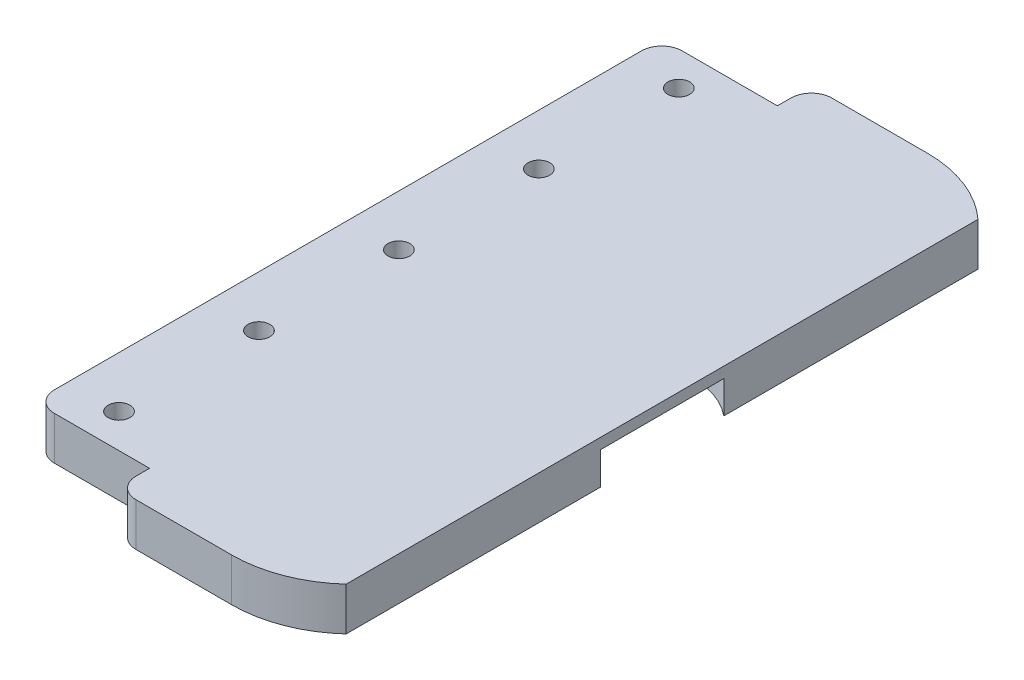
SolidWorks part; units mm, degrees
ref_plane "Front Plane" through (0, 0, 0) normal (0, 0, 1) x (1, 0, 0)
ref_plane "Top Plane" through (0, 0, 0) normal (0, 1, 0) x (1, 0, 0)
ref_plane "Right Plane" through (0, 0, 0) normal (1, 0, 0) x (0, 0, -1)
sketch "Sketch1" plane through (0, 0, 0) normal (0, 1, 0) x (1, 0, 0)
  line L0 (7.5, 102.362) -> (7.5, 0) construction
  line L1 (0, 0) -> (52.084, 0)
  line L2 (0, 0) -> (0, 102.362)
  line L3 (0, 102.362) -> (52.084, 102.362)
  line L4 (52.084, 0) -> (52.084, 102.362)
  line L5 (30.3604, 43.18) -> (30.3604, 59.18)
  line L6 (17, 0) -> (0, 0)
  line L7 (17, 0) -> (17, 5)
  line L8 (17, 5) -> (0, 5)
  line L9 (0, 0) -> (0, 5)
  line L10 (0, 102.362) -> (17, 102.362)
  line L11 (0, 102.362) -> (0, 97.362)
  line L12 (0, 97.362) -> (17, 97.362)
  line L13 (17, 102.362) -> (17, 97.362)
  circle A0 centre (38.876, 95.63) radius 3.556
  arc A1 (30.3604, 43.18) -> (30.3604, 59.18) centre (38.876, 51.18) ccw
  circle A2 centre (38.876, 6.73) radius 3.556
  circle A3 centre (7.5, 92.362) radius 1.6
  circle A4 centre (7.5, 71.772) radius 1.6
  circle A5 centre (7.5, 51.182) radius 1.6
  circle A6 centre (7.5, 30.592) radius 1.6
  circle A7 centre (7.5, 10.002) radius 1.6
  point P31 (0, 0)
  point P32 (0, 0)
  dimension "D3" = 7.112
  dimension "D4" = 7.112
  dimension "D5" = 23.368
  dimension "D11" = 3.2
  dimension "D1" = 102.362
  dimension "D2" = 52.084
  dimension "D6" = 44.45
  dimension "D7" = 44.45
  dimension "D8" = 51.18
  dimension "D9" = 13.208
  dimension "D10" = 7.5
  dimension "D12" = 10
  dimension "D14" = 17
  dimension "D15" = 5
  dimension "D16" = 17
  dimension "D17" = 5
  dimension "D18" = 20.59
  dimension "D19" = 16
  dimension "D13" = 5
extrude "Boss-Extrude1" add sketch "Sketch1" along normal blind 6.35 contours L1 L4 L3 L2
extrude "Cut-Extrude2" cut sketch "Sketch1<4>" along normal through all contours A4 L0 | L0 A4 | A3 | A5 | A6 | A7 region at (8.1791, 0, -71.772) region at (6.8209, 0, -71.772)
sketch "Sketch1<4>" plane through (0, 0, 0) normal (0, 1, 0) x (1, 0, 0) same geometry as "Sketch1"
extrude "Cut-Extrude3" cut sketch "Sketch1<5>" along normal offset from surface (4.7625 mm away) 1.5875 contours A1 | A0 | A2 region at (39.7422, 0, -51.18) region at (38.876, 0, -95.63) up to face at (7.5, 6.35, -8.402)
sketch "Sketch1<5>" plane through (0, 0, 0) normal (0, 1, 0) x (1, 0, 0) same geometry as "Sketch1"
fillet "Fillet1" radius 18 2 edges at (52.084, 3.175, -102.362) (52.084, 3.175, 0)
extrude "Cut-Extrude4" cut sketch "Sketch1<7>" along normal through all contours L6 L7 L8 L9 | L10 L13 L12 L11
sketch "Sketch1<7>" plane through (0, 0, 0) normal (0, 1, 0) x (1, 0, 0) same geometry as "Sketch1"
fillet "Fillet4" radius 3 4 edges at (17, 3.175, -102.362) (0, 3.175, -97.362) (0, 3.175, -5) (17, 3.175, 0)
sketch "Sketch3" plane through (0, 0, 0) normal (0, -1, 0) x (1, 0, 0)
  line L1 (46.2193, -4.7058) -> (68.6711, -4.7058)
  line L2 (46.2193, -4.7058) -> (46.2193, -97.6562)
  line L3 (46.2193, -97.6562) -> (68.6711, -97.6562)
  line L4 (68.6711, -4.7058) -> (68.6711, -97.6562)
  arc A0 (52.084, -18) -> (34.084, 0) centre (34.084, -18) ccw construction
  arc A1 (34.084, -102.362) -> (52.084, -84.362) centre (34.084, -84.362) ccw construction
  point P7 (48.4069, -7.098)
  point P8 (49.0464, -94.3683)
  point P12 (46.2193, -4.7058)
extrude "Cut-Extrude6" cut sketch "Sketch3" against normal blind 6.35
